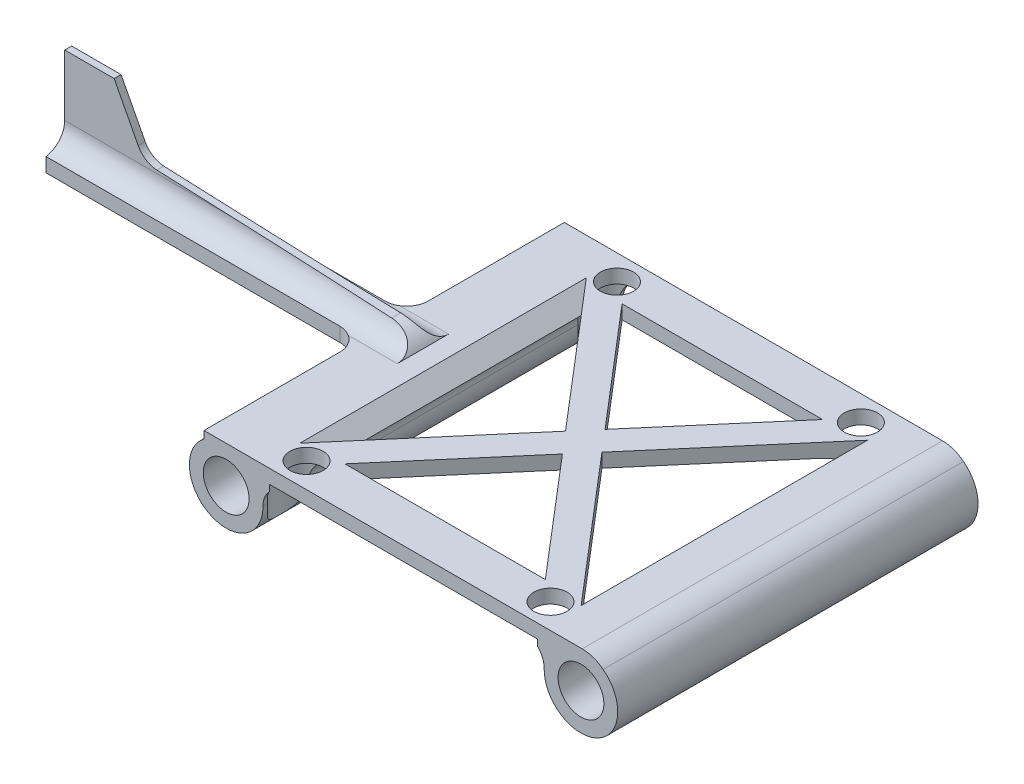
SolidWorks part; units mm, degrees
ref_plane "Front Plane" through (0, 0, 0) normal (0, 0, 1) x (1, 0, 0)
ref_plane "Top Plane" through (0, 0, 0) normal (0, 1, 0) x (1, 0, 0)
ref_plane "Right Plane" through (0, 0, 0) normal (1, 0, 0) x (0, 0, -1)
sketch "Sketch2" plane through (0, 0, 0) normal (0, 1, 0) x (1, 0, 0)
  line L0 (0, -20.6375) -> (0, 20.6375)
  line L4 (-81.915, -2.54) -> (-81.915, 2.54)
  line L5 (0, 20.6375) -> (-45.72, 20.6375)
  line L6 (-45.72, 20.6375) -> (-45.72, 2.54)
  line L7 (-81.915, 2.54) -> (-45.72, 2.54)
  line L8 (0, -20.6375) -> (-45.72, -20.6375)
  line L9 (-45.72, -20.6375) -> (-45.72, -2.54)
  line L10 (-45.72, -2.54) -> (-81.915, -2.54)
  point P0 (0, 0)
  dimension "D1" = 41.275
  dimension "D2" = 81.915
  dimension "D3" = 5.08
  dimension "D4" = 45.72
extrude "Boss-Extrude1" add sketch "Sketch2" along normal blind 1.5875
sketch "Sketch3" plane through (0, 0, 20.6375) normal (0, 0, 1) x (1, 0, 0)
  line L1 (-45.72, 0) -> (-43.18, 0) construction
  line L2 (0, 0) -> (-45.72, 0) construction
  line L3 (0, 0) -> (-2.54, 0) construction
  line L4 (0, 0) -> (-45.72, 0) construction
  line L5 (-45.72, 1.5875) -> (0, 1.5875) construction
  circle A0 centre (-43.18, -2.625) radius 2.625
  circle A1 centre (-2.54, -2.625) radius 2.625
  circle A2 centre (-43.18, -2.625) radius 4.2125
  circle A3 centre (-2.54, -2.625) radius 4.2125
  dimension "D2" = 5.25
  dimension "D1" = 40.64
extrude "Boss-Extrude2" add sketch "Sketch3" against normal blind 41.275
fillet "Fillet1" radius 2.54 2 edges at (-5.8346, 0, 0) (-39.8854, 0, 0)
sketch "Sketch4" plane through (-81.915, 0, 0) normal (-1, 0, 0) x (0, 0, 1)
  line L0 (-0.3969, 1.5875) -> (-0.3969, 11.1125)
  line L1 (-2.54, 1.5875) -> (2.54, 1.5875) construction
  line L2 (-0.3969, 11.1125) -> (0.3969, 11.1125)
  line L3 (0.3969, 11.1125) -> (0.3969, 1.5875)
  line L4 (-2.54, 1.5875) -> (-0.3969, 1.5875)
  line L5 (2.54, 1.5875) -> (0.3969, 1.5875)
  line L6 (-0.3969, 1.5875) -> (0.3969, 1.5875)
  line M7 (2.54, 1.5875) -> (-2.54, 1.5875)
  dimension "D1" = 0.7937
  dimension "D2" = 9.525
extrude "Boss-Extrude3" add sketch "Sketch4" against normal blind 40.64 contours L3 L2 L0 M7 region at (-81.915, 6.35, 0)
sketch "Sketch5" plane through (0, 0, 0.3969) normal (0, 0, 1) x (1, 0, 0)
  line L4 (-41.275, 3.2443) -> (-72.82, 4.5432)
  line L5 (-72.82, 4.5432) -> (-76.2508, 11.1125)
  line L6 (-41.275, 11.1125) -> (-81.915, 11.1125) construction
  line L7 (-76.2508, 11.1125) -> (-41.275, 11.1125)
  line L8 (-41.275, 11.1125) -> (-41.275, 3.2443)
  point P2 (0, 0)
  point P4 (-41.275, 2.8732)
  point P7 (0, 0)
  point P8 (-41.275, 3.2443)
  dimension "D1" = 5.6642
extrude "Cut-Extrude2" cut sketch "Sketch5" against normal blind 31.115
fillet "Fillet2" radius 2.54 2 edges at (-61.595, 1.5875, 0.3969) (-61.595, 1.5875, -0.3969)
fillet "Fillet3" radius 2.54 2 edges at (-45.72, 1.1771, -2.54) (-45.72, 1.1771, 2.54)
sketch "Sketch6" plane through (0, 1.5875, 0) normal (0, 1, 0) x (1, 0, 0)
  line L0 (-36.428, 15.875) -> (-36.428, -15.875)
  line L1 (-36.428, -20.6375) -> (-36.428, 20.6375) construction
  line L2 (-36.428, -15.875) -> (-9.292, 15.875)
  line L3 (-9.292, 20.6375) -> (-9.292, -20.6375) construction
  line L4 (-9.292, 15.875) -> (-9.292, -15.875)
  line L5 (-9.292, -15.875) -> (-36.428, 15.875)
  line L6 (-36.428, 15.875) -> (-9.292, 15.875)
  line L7 (-36.428, -15.875) -> (-9.292, -15.875)
  line L8 (0, -20.6375) -> (-45.72, -20.6375) construction
  line L9 (0, 20.6375) -> (-45.72, 20.6375) construction
  line L10 (-8.0852, -14.8436) -> (-35.2212, 16.9064)
  line L11 (-10.4988, -16.9064) -> (-37.6348, 14.8436)
  line L12 (-35.2212, -16.9064) -> (-8.0852, 14.8436)
  line L13 (-37.6348, -14.8436) -> (-10.4988, 16.9064)
  dimension "D1" = 4.7625
  dimension "D2" = 4.7625
  dimension "D3" = 1.5875
  dimension "D4" = 1.5875
  dimension "D5" = 1.5875
  dimension "D6" = 1.5875
extrude "Cut-Extrude3" cut sketch "Sketch6" against normal blind 31.115 contours L0 L13 L11 | L10 L13 L6 | L12 L10 L4 | L12 L7 L11 region at (-32.6015, 1.5875, 0) region at (-22.86, 1.5875, -11.3978) region at (-22.86, 1.5875, 11.3978) region at (-13.1185, 1.5875, 0)
fillet "Fillet4" radius 2.54 1 edges at (-72.82, 4.5432, 0)
sketch "Sketch7" plane through (0, 1.5875, 0) normal (0, 1, 0) x (1, 0, 0)
  line L0 (-45.72, 17.78) -> (-36.83, 17.78) construction
  line L1 (0, -20.6375) -> (-45.72, -20.6375) construction
  line L2 (0, -20.6375) -> (0, 20.6375) construction
  line L3 (0, 20.6375) -> (-45.72, 20.6375) construction
  line L4 (-45.72, -20.6375) -> (-45.72, 20.6375) construction
  line L5 (-8.89, 17.78) -> (0, 17.78) construction
  line L6 (-45.72, -17.78) -> (-36.83, -17.78) construction
  line L7 (0, -17.78) -> (-8.89, -17.78) construction
  line L8 (-8.89, -17.78) -> (-8.89, -20.6375) construction
  line L9 (-8.89, 17.78) -> (-8.89, 20.6375) construction
  circle A0 centre (-36.83, 17.78) radius 1.905
  circle A1 centre (-8.89, 17.78) radius 1.905
  circle A2 centre (-36.83, -17.78) radius 1.905
  circle A3 centre (-8.89, -17.78) radius 1.905
  dimension "D2" = 3.81
  dimension "D1" = 27.94
  dimension "D3" = 35.56
extrude "Cut-Extrude4" cut sketch "Sketch7" against normal blind 31.115 contours A0 | A1 | A3 | A2 region at (-36.83, 1.5875, -17.78) region at (-8.89, 1.5875, -17.78) region at (-36.83, 1.5875, 17.78) region at (-8.89, 1.5875, 17.78)
chamfer "Chamfer1" distance 2.54 angle 45 2 edges at (-9.292, 1.5875, 0) (-36.428, 1.5875, 0)
sketch "Sketch8" plane through (0, 0, 0) normal (0, -1, 0) x (1, 0, 0)
  circle A0 centre (-8.89, -17.78) radius 3.175
  circle A1 centre (-36.83, -17.78) radius 3.175
  circle A2 centre (-36.83, 17.78) radius 3.175
  circle A3 centre (-8.89, 17.78) radius 3.175
  dimension "D1" = 6.35
extrude "Cut-Extrude5" cut sketch "Sketch8" along normal blind 31.115
fillet "Fillet5" radius 3.81 1 edges at (0, 1.5875, 0)
fillet "Fillet6" radius 3.81 1 edges at (-41.275, 3.2443, 0)
sketch "Sketch9" plane through (-81.915, 0, 0) normal (-1, 0, 0) x (0, 0, 1)
  line L0 (-2.54, 0) -> (-0.3969, 0)
  line L1 (3.2733, 0) -> (-3.2733, 0) construction
  line L2 (-0.3969, 0) -> (-0.3969, -1.5875)
  line L3 (-0.3969, -1.5875) -> (0.3969, -1.5875)
  line L4 (0.3969, -1.5875) -> (0.3969, 0)
  line L5 (-2.54, 0) -> (2.54, 0) construction
  line L6 (0.3969, 0) -> (2.54, 0)
  line L13 (-2.54, 0) -> (2.54, 0)
  line L14 (2.54, 0) -> (2.54, 1.6187)
  line L15 (0.3969, 4.1275) -> (0.3969, 11.1125)
  line L16 (0.3969, 11.1125) -> (-0.3969, 11.1125)
  line L17 (-0.3969, 11.1125) -> (-0.3969, 4.1275)
  line L18 (-2.54, 1.6187) -> (-2.54, 0)
  line L19 (-2.54, 0) -> (2.54, 0)
  arc A2 (0.3969, 4.1275) -> (2.54, 1.6187) centre (2.9369, 4.1275) ccw
  arc A3 (-2.54, 1.6187) -> (-0.3969, 4.1275) centre (-2.9369, 4.1275) ccw
  line M14 (-2.54, 0) -> (2.54, 0)
  dimension "D1" = 0.7937
  dimension "D2" = 1.5875
  dimension "D3" = 0
extrude "Boss-Extrude4" add sketch "Sketch9" against normal blind 36.195 contours L3 L4 L2 M14 region at (-81.915, -0.7938, 0)
sketch "Sketch10" plane through (0, 0, 0.3969) normal (0, 0, 1) x (1, 0, 0)
  line L0 (-54.8743, -1.5875) -> (-59.746, 0)
  line L1 (-47.2627, -1.5875) -> (-81.915, -1.5875) construction
  line L2 (-81.915, 0) -> (-48.26, 0) construction
  line L3 (-59.746, 0) -> (-81.915, 0)
  line L4 (-81.915, 0) -> (-81.915, -1.5875)
  line L5 (-81.915, -1.5875) -> (-54.8743, -1.5875)
extrude "Cut-Extrude6" cut sketch "Sketch10" against normal blind 36.195
fillet "Fillet7" radius 3.81 1 edges at (-54.8743, -1.5875, 0)
ref_plane "Plane1" through (-47.3925, 0, 0) normal (-1, 0, 0) x (0, 0, 1)
sketch "Sketch11" plane through (0, 1.5875, 0) normal (0, 1, 0) x (1, 0, 0)
  line L0 (-47.3925, -14.2564) -> (-28.1787, 0)
  line L1 (-47.3925, 4.6338) -> (-47.3925, -4.6338) construction
  line L2 (-28.1787, 0) -> (-47.3925, 14.2564)
  line L3 (-47.3925, 20.6375) -> (-47.3925, 14.2564)
  line L4 (-38.9675, 20.6375) -> (-47.3925, 20.6375) construction
  line L5 (-47.3925, -20.6375) -> (-47.3925, -14.2564)
  line L6 (-47.3925, -20.6375) -> (-38.9675, -20.6375) construction
  point P6 (-47.3925, -20.6375)
  dimension "D1" = 73.15
  dimension "D2" = 19.2138
ref_plane "Plane2" through (-47.3925, 1.5875, -14.2564) normal (-0.8031, 0, -0.5959) x (-0.5959, 0, 0.8031)
ref_plane "Plane3" through (-47.3925, 1.5875, 14.2564) normal (0.8031, 0, -0.5959) x (-0.5959, 0, -0.8031)
